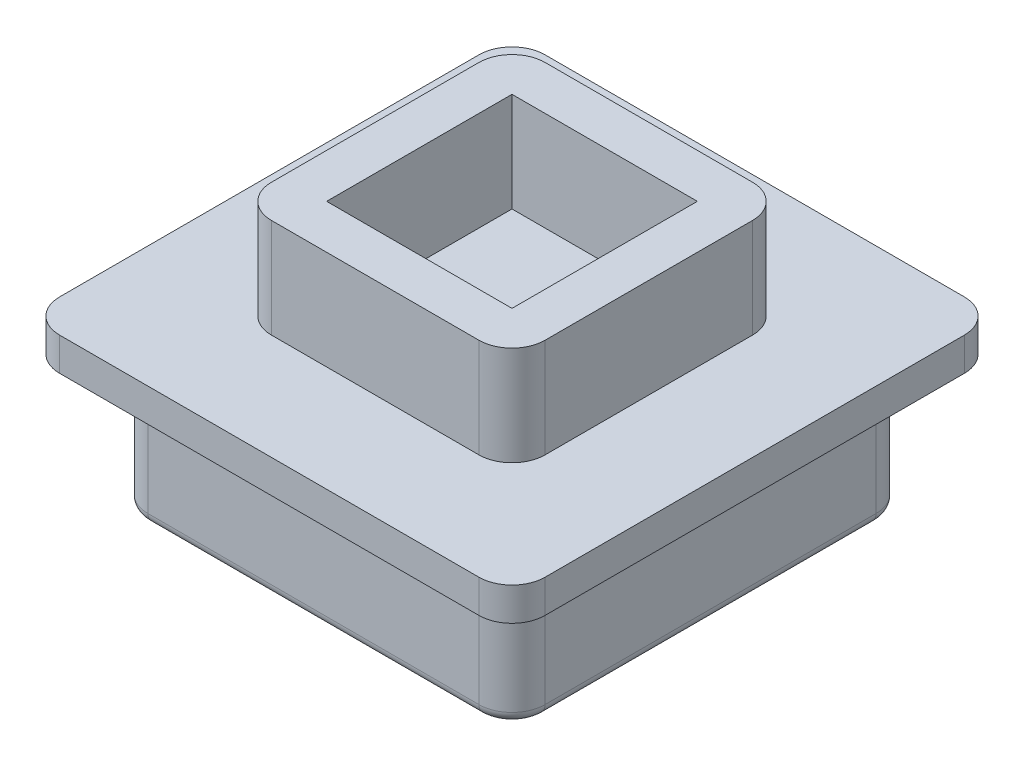
SolidWorks part; units mm, degrees
ref_plane "Front Plane" through (0, 0, 0) normal (0, 0, 1) x (1, 0, 0)
ref_plane "Top Plane" through (0, 0, 0) normal (0, 1, 0) x (1, 0, 0)
ref_plane "Right Plane" through (0, 0, 0) normal (1, 0, 0) x (0, 0, -1)
sketch "Sketch1" plane through (0, 0, 0) normal (0, 1, 0) x (1, 0, 0)
  line L1 (-4.5, -4.5) -> (4.5, -4.5)
  line L2 (-4.5, -4.5) -> (-4.5, 4.5)
  line L3 (-4.5, 4.5) -> (4.5, 4.5)
  line L4 (4.5, -4.5) -> (4.5, 4.5)
  line L5 (-4.5, -4.5) -> (4.5, 4.5) construction
  line L6 (-4.5, 4.5) -> (4.5, -4.5) construction
  point P0 (0, 0)
  dimension "D1" = 9
  dimension "D2" = 9
extrude "Boss-Extrude1" add sketch "Sketch1" along normal blind 3
sketch "Sketch2" plane through (0, 3, 0) normal (0, 1, 0) x (1, 0, 0)
  line L8 (5.5, -5.5) -> (5.5, 5.5)
  line L9 (5.5, 5.5) -> (-5.5, 5.5)
  line L10 (-5.5, 5.5) -> (-5.5, -5.5)
  line L11 (-5.5, -5.5) -> (5.5, -5.5)
  line L12 (5.5, -5.5) -> (5.5, 5.5)
  line L13 (5.5, 5.5) -> (-5.5, 5.5)
  line L14 (-5.5, 5.5) -> (-5.5, -5.5)
  line L15 (-5.5, -5.5) -> (5.5, -5.5)
  dimension "D1" = 1
extrude "Boss-Extrude2" add sketch "Sketch2" along normal blind 0.75
sketch "Sketch3" plane through (0, 3.75, 0) normal (0, 1, 0) x (1, 0, 0)
  line L0 (-3.1, 3.1) -> (3.1, 3.1)
  line L1 (-2.1, -2.1) -> (2.1, -2.1)
  line L2 (-2.1, -2.1) -> (-2.1, 2.1)
  line L3 (-2.1, 2.1) -> (2.1, 2.1)
  line L4 (2.1, -2.1) -> (2.1, 2.1)
  line L5 (-2.1, -2.1) -> (2.1, 2.1) construction
  line L6 (-2.1, 2.1) -> (2.1, -2.1) construction
  line L7 (3.1, -3.1) -> (3.1, 3.1)
  line L8 (-3.1, -3.1) -> (3.1, -3.1)
  line L9 (-3.1, -3.1) -> (-3.1, 3.1)
  point P0 (0, 0)
  dimension "D1" = 4.2
  dimension "D2" = 4.2
  dimension "D3" = 1
extrude "Boss-Extrude3" add sketch "Sketch3" along normal blind 2.25
fillet "Fillet1" radius 0.75 12 edges at (-3.1, 4.875, 3.1) (-3.1, 4.875, -3.1) (3.1, 4.875, -3.1) (3.1, 4.875, 3.1) (5.5, 3.375, 5.5) (-5.5, 3.375, 5.5) (-5.5, 3.375, -5.5) (5.5, 3.375, -5.5) (4.5, 1.5, -4.5) (-4.5, 1.5, -4.5) (-4.5, 1.5, 4.5) (4.5, 1.5, 4.5)
fillet "Fillet2" radius 0.25 8 edges at (4.2803, 0, -4.2803) (4.5, 0, 0) (4.2803, 0, 4.2803) (0, 0, 4.5) (-4.2803, 0, 4.2803) (-4.5, 0, 0) (-4.2803, 0, -4.2803) (0, 0, -4.5)
